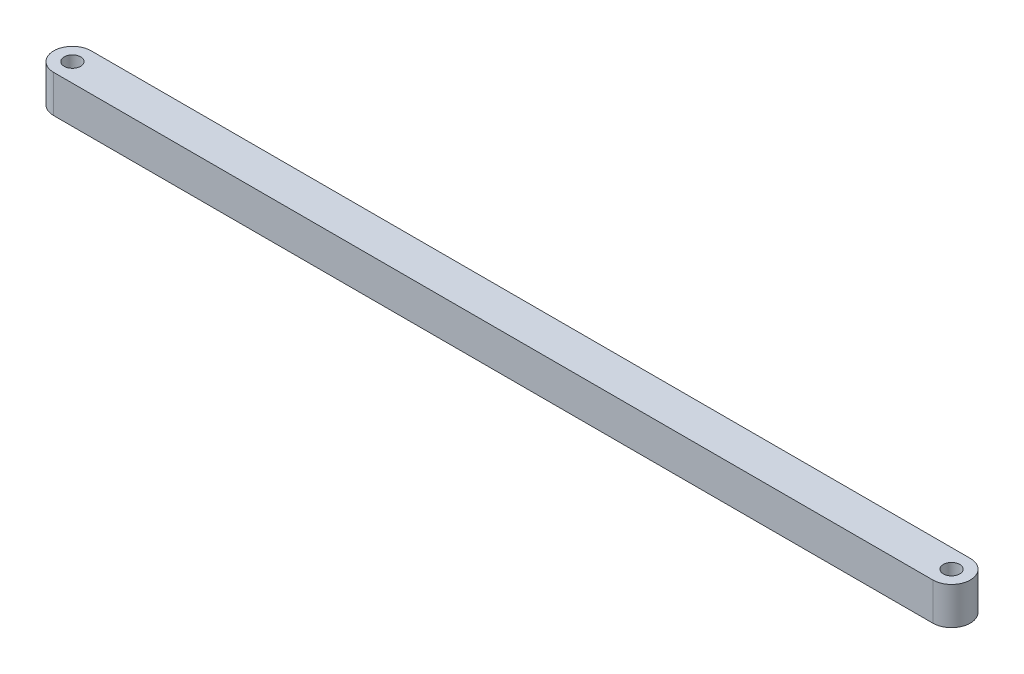
SolidWorks part; units mm, degrees
ref_plane "Front Plane" through (0, 0, 0) normal (0, 0, 1) x (1, 0, 0)
ref_plane "Top Plane" through (0, 0, 0) normal (0, 1, 0) x (1, 0, 0)
ref_plane "Right Plane" through (0, 0, 0) normal (1, 0, 0) x (0, 0, -1)
sketch "Sketch1" plane through (0, 0, 0) normal (0, 1, 0) x (1, 0, 0)
  line L1 (-58.7, 2.5) -> (58.7, 2.5)
  line L2 (58.7, -2.5) -> (-58.7, -2.5)
  circle A0 centre (-58.7, 0) radius 1.1
  circle A1 centre (58.7, 0) radius 1.1
  arc A2 (-58.7, 2.5) -> (-58.7, -2.5) centre (-58.7, 0) ccw
  arc A3 (58.7, -2.5) -> (58.7, 2.5) centre (58.7, 0) ccw
  point P4 (0, 0)
  dimension "D1" = 2.2
  dimension "D2" = 2.2
  dimension "D3" = 5
  dimension "D4" = 5
extrude "Boss-Extrude1" add sketch "Sketch1" along normal blind 5
